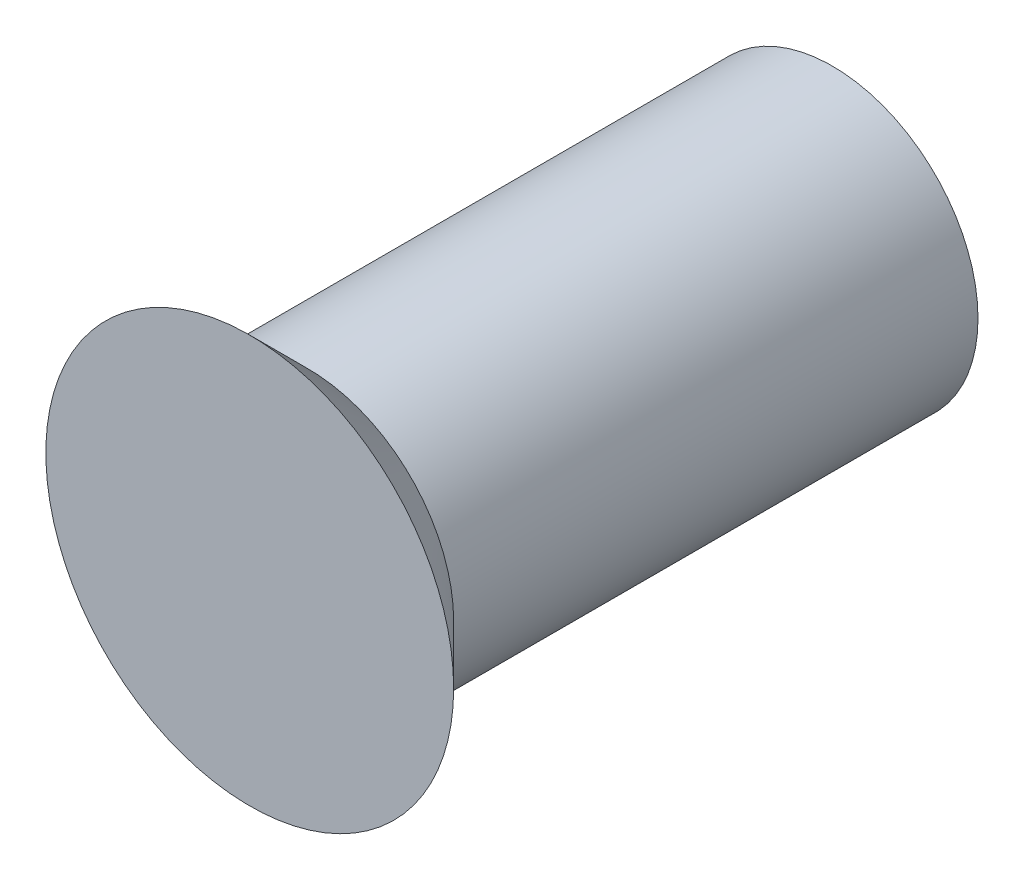
SolidWorks part; units mm, degrees
ref_plane "Ön Düzlem" through (0, 0, 0) normal (0, 0, 1) x (1, 0, 0)
ref_plane "Üst Düzlem" through (0, 0, 0) normal (0, 1, 0) x (1, 0, 0)
ref_plane "Sağ Düzlem" through (0, 0, 0) normal (1, 0, 0) x (0, 0, -1)
sketch "Çizim1" plane through (0, 0, 0) normal (0, 0, 1) x (1, 0, 0)
  circle A0 centre (0, 0) radius 2.5
  dimension "D1" = 5
extrude "Yükseklik-Ekstrüzyon1" add sketch "Çizim1" along normal blind 9
sketch "Çizim2" plane through (0, 0, 9) normal (0, 0, 1) x (1, 0, 0)
  circle A0 centre (0, 0) radius 2.5
extrude "Yükseklik-Ekstrüzyon2" add sketch "Çizim2" along normal blind 1 draft 45 draft outward yes
